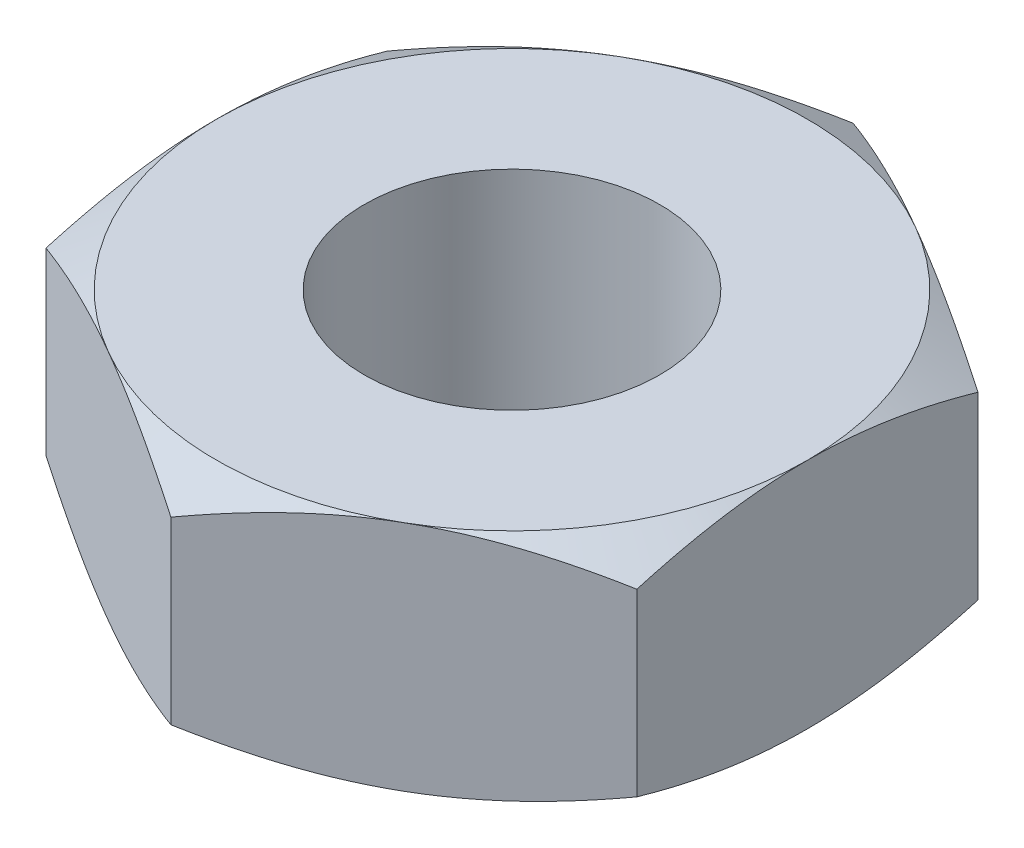
SolidWorks part; units mm, degrees
ref_plane "Front Plane" through (0, 0, 0) normal (0, 0, 1) x (1, 0, 0)
ref_plane "Top Plane" through (0, 0, 0) normal (0, 1, 0) x (1, 0, 0)
ref_plane "Right Plane" through (0, 0, 0) normal (1, 0, 0) x (0, 0, -1)
sketch "Sketch1" plane through (0, 0, 0) normal (0, 1, 0) x (1, 0, 0)
  line L1 (12.7, 7.3323) -> (0, 14.6647)
  line L2 (0, 14.6647) -> (-12.7, 7.3323)
  line L3 (-12.7, 7.3323) -> (-12.7, -7.3323)
  line L4 (-12.7, -7.3323) -> (0, -14.6647)
  line L5 (0, -14.6647) -> (12.7, -7.3323)
  line L6 (12.7, -7.3323) -> (12.7, 7.3323)
  circle A0 centre (0, 0) radius 12.7 construction
  dimension "D1" = 25.4
extrude "Boss-Extrude1" add sketch "Sketch1" along normal mid plane 10
sketch "Sketch2" plane through (0, 5, 0) normal (0, 1, 0) x (1, 0, 0)
  circle A0 centre (0, 0) radius 6.35
  dimension "D1" = 12.7
extrude "Cut-Extrude1" cut sketch "Sketch2" against normal through all
cosmetic thread "Cosmetic Thread1" parameters "D2"=14.2875
sketch "Sketch3" plane through (0, 5, 0) normal (0, 1, 0) x (1, 0, 0)
  circle A0 centre (0, 0) radius 12.7
extrude "Cut-Extrude2" cut sketch "Sketch3" against normal through all draft 60 flip side to cut
mirror "Mirror1" about plane through (0, 0, 0) normal (0, 1, 0) of "Cut-Extrude2"
